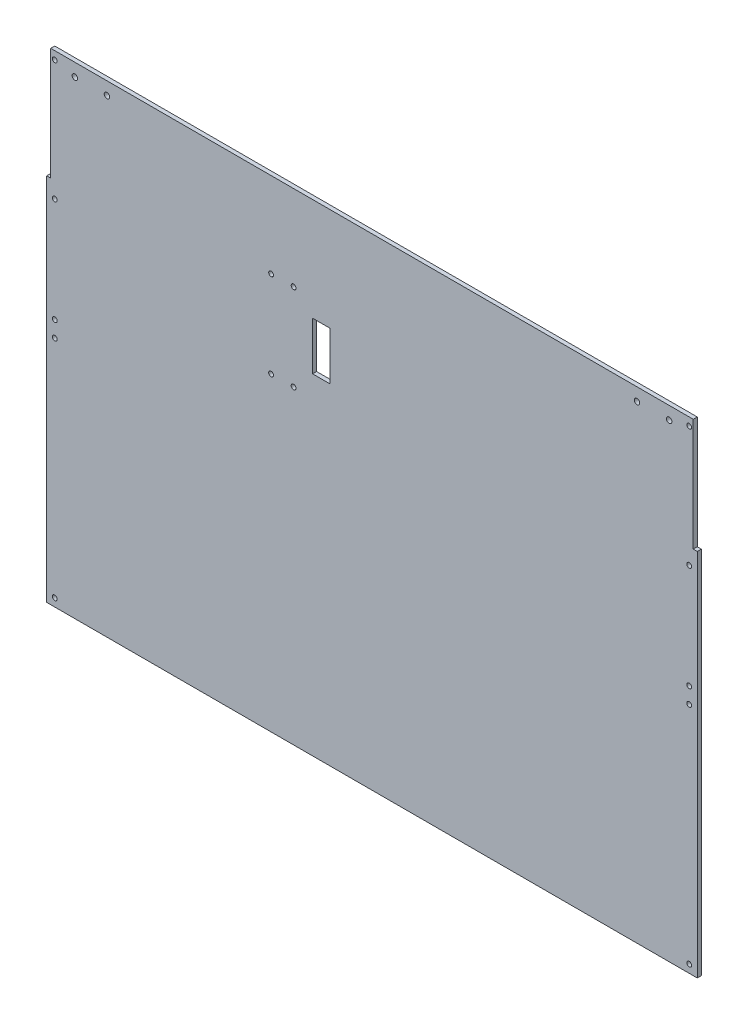
SolidWorks part; units mm, degrees
ref_plane "Front Plane" through (0, 0, 0) normal (0, 0, 1) x (1, 0, 0)
ref_plane "Top Plane" through (0, 0, 0) normal (0, 1, 0) x (1, 0, 0)
ref_plane "Right Plane" through (0, 0, 0) normal (1, 0, 0) x (0, 0, -1)
sketch "Sketch1" plane through (0, 0, 0) normal (0, 0, 1) x (1, 0, 0)
  line L1 (-254, -190.5) -> (254, -190.5)
  line L2 (-254, -190.5) -> (-254, 190.5)
  line L3 (-254, 190.5) -> (254, 190.5)
  line L4 (254, -190.5) -> (254, 190.5)
  line L5 (-254, -190.5) -> (254, 190.5) construction
  line L6 (-254, 190.5) -> (254, -190.5) construction
  point P0 (0, 0)
  dimension "D1" = 508
  dimension "D2" = 381
extrude "Boss-Extrude1" add sketch "Sketch1" along normal blind 3.175
sketch "Sketch3" plane through (0, 0, 3.175) normal (0, 0, 1) x (1, 0, 0)
  line L0 (-254, 190.5) -> (-254, -190.5) construction
  line L1 (-46.99, 71.12) -> (-33.02, 71.12)
  line L2 (-46.99, 71.12) -> (-46.99, 109.22)
  line L3 (-46.99, 109.22) -> (-33.02, 109.22)
  line L4 (-33.02, 71.12) -> (-33.02, 109.22)
  line L5 (254, 190.5) -> (-254, 190.5) construction
  dimension "D1" = 207.01
  dimension "D2" = 13.97
  dimension "D3" = 119.38
  dimension "D4" = 38.1
extrude "Cut-Extrude2" cut sketch "Sketch3" against normal up to surface (3.175 mm away) up to face at (0, 0, 0)
sketch "Sketch2" plane through (0, 0, 3.175) normal (0, 0, 1) x (1, 0, 0)
  line L1 (254, 190.5) -> (-254, 190.5) construction
  line L2 (-254, -190.5) -> (254, -190.5) construction
  line L3 (250.825, 190.5) -> (250.825, -190.5) construction
  line L4 (254, -190.5) -> (254, 190.5) construction
  line L6 (0, 0) -> (0, -50000) construction
  line L8 (-33.02, 109.22) -> (-46.99, 109.22) construction
  line L10 (254, 190.5) -> (-254, 190.5) construction
  circle A2 centre (250.825, 184.15) radius 1.905
  circle A3 centre (250.825, -184.15) radius 1.905
  circle A12 centre (-79.7747, 123.19) radius 1.905
  circle A13 centre (-79.7747, 54.61) radius 1.905
  circle A14 centre (-61.9947, 123.19) radius 1.905
  circle A15 centre (-61.9947, 54.61) radius 1.905
  circle A16 centre (-250.825, 184.15) radius 1.905
  circle A17 centre (-250.825, 88.9) radius 1.905
  circle A18 centre (250.825, 88.9) radius 1.905
  circle A19 centre (250.825, 6.35) radius 1.905
  circle A20 centre (250.825, -6.35) radius 1.905
  circle A21 centre (-250.825, 6.35) radius 1.905
  circle A22 centre (-250.825, -6.35) radius 1.905
  circle A23 centre (-250.825, -184.15) radius 1.905
  point P33 (0, -190.5)
  dimension "D14" = 3.81
  dimension "D12" = 17.78
  dimension "D18" = 3.81
  dimension "D1" = 3.175
  dimension "D5" = 6.35
  dimension "D6" = 6.35
  dimension "D11" = 177.8
  dimension "D13" = 68.58
  dimension "D15" = 15.0047
  dimension "D16" = 13.97
  dimension "D17" = 177.8
  dimension "D19" = 101.6
extrude "Cut-Extrude1" cut sketch "Sketch2" against normal blind 3.175
sketch "Sketch4" plane through (0, 0, 3.175) normal (0, 0, 1) x (1, 0, 0)
  line L0 (254, -190.5) -> (254, 190.5) construction
  line L1 (254, 101.6) -> (257.175, 101.6)
  line L2 (254, 101.6) -> (254, -190.5)
  line L3 (254, -190.5) -> (257.175, -190.5)
  line L4 (257.175, 101.6) -> (257.175, -190.5)
  line L5 (-254, -190.5) -> (254, -190.5) construction
  line L6 (254, 190.5) -> (-254, 190.5) construction
  line L7 (0, 190.5) -> (0, -190.5) construction
  line L8 (-254, -190.5) -> (-257.175, -190.5)
  line L9 (-254, 101.6) -> (-257.175, 101.6)
  line L10 (-254, 101.6) -> (-254, -190.5)
  line L11 (-257.175, 101.6) -> (-257.175, -190.5)
  dimension "D1" = 3.175
  dimension "D2" = 88.9
extrude "Boss-Extrude2" add sketch "Sketch4" against normal blind 3.175
sketch "Sketch5" plane through (0, 0, 0) normal (0, 0, -1) x (-1, 0, 0)
  line L0 (254, 190.5) -> (254, 101.6) construction
  line L1 (-254, 190.5) -> (254, 190.5) construction
  line L2 (-254, 101.6) -> (-254, 190.5) construction
  circle A0 centre (234.95, 180.34) radius 2.159
  circle A1 centre (209.55, 180.34) radius 2.159
  circle A2 centre (-234.95, 180.34) radius 2.159
  circle A3 centre (-209.55, 180.34) radius 2.159
  dimension "D3" = 4.318
  dimension "D1" = 19.05
  dimension "D2" = 44.45
  dimension "D4" = 10.16
  dimension "D5" = 19.05
  dimension "D6" = 44.45
extrude "Cut-Extrude3" cut sketch "Sketch5" against normal through all
